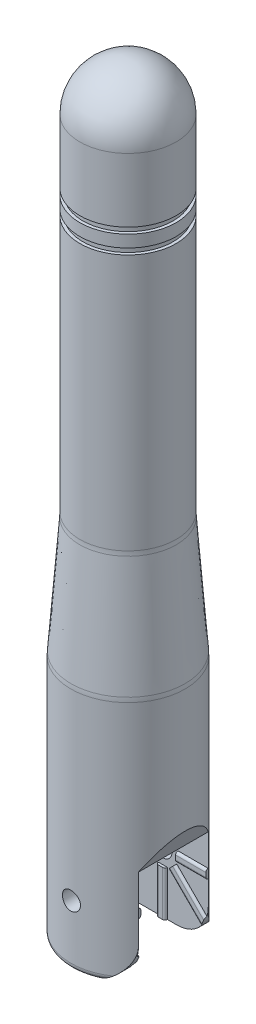
SolidWorks part; units mm, degrees
ref_plane "Plan de face" through (0, 0, 0) normal (0, 0, 1) x (1, 0, 0)
ref_plane "Plan de dessus" through (0, 0, 0) normal (0, 1, 0) x (1, 0, 0)
ref_plane "Plan de droite" through (0, 0, 0) normal (1, 0, 0) x (0, 0, -1)
sketch "Esquisse2" plane through (0, 0, 0) normal (0, 0, 1) x (1, 0, 0)
  line L0 (0, 0) -> (0, 63.1604) construction
  line L1 (0, 63.1604) -> (4, 63.1604) construction
  line L2 (4, 63.1604) -> (4, 0) construction
  line L3 (4, 0) -> (0, 0) construction
  line L4 (4, 0) -> (4.75, 0) construction
  line L5 (4.75, 0) -> (4.75, 20.4) construction
  line L6 (4.75, 20.4) -> (0, 20.4) construction
  line L7 (4, 59.1604) -> (4, 30.5872) construction
  line L8 (4.014, 30.2133) -> (4.736, 20.5867)
  line L9 (4.75, 20.2128) -> (4.75, 0)
  line L10 (4.75, 0) -> (1, 0)
  line L11 (1, 0) -> (1, 59.1604)
  line L12 (1, 59.1604) -> (0, 59.1604)
  line L13 (4, 59.1604) -> (4, 53.8604)
  line L14 (4, 53.8604) -> (3.75, 53.8604)
  line L15 (3.75, 53.8604) -> (3.75, 53.3604)
  line L16 (3.75, 53.3604) -> (4, 53.3604)
  line L17 (4, 53.3604) -> (4, 52.3604)
  line L18 (4, 52.3604) -> (3.75, 52.3604)
  line L19 (3.75, 52.3604) -> (3.75, 51.8604)
  line L20 (3.75, 51.8604) -> (4, 51.8604)
  line L21 (0, 63.1604) -> (0, 59.1604)
  line L22 (4, 51.8604) -> (4, 30.5872)
  arc A0 (0, 63.1604) -> (4, 59.1604) centre (0, 59.1604) cw
  arc A1 (4.75, 20.2128) -> (4.736, 20.5867) centre (-0.25, 20.2128) ccw
  arc A2 (4.014, 30.2133) -> (4, 30.5872) centre (9, 30.5872) cw
  point P18 (4, 30.4)
  point P25 (3.875, 52.3604)
  dimension "D7" = 5
  dimension "D1" = 63.1604
  dimension "D2" = 8
  dimension "D3" = 9.5
  dimension "D4" = 20.4
  dimension "D5" = 2
  dimension "D6" = 10
  dimension "D8" = 9.3
  dimension "D9" = 0.5
  dimension "D10" = 1.5
  dimension "D11" = 7.5
revolve "Révolution1" add sketch "Esquisse2" angle 360 about L0
sketch "Esquisse3" plane through (0, 0, 0) normal (0, -1, 0) x (1, 0, 0)
  line L0 (0, 0) -> (-2.75, 0) construction
  line L1 (-2.75, 2.9) -> (4.75, 2.9)
  line L2 (-2.75, 2.9) -> (-2.75, -2.9)
  line L3 (-2.75, -2.9) -> (4.75, -2.9)
  line L4 (4.75, 2.9) -> (4.75, -2.9)
  line L5 (-4.75, 0) -> (-2.75, 0) construction
  circle A0 centre (0, 0) radius 4.75 construction
  dimension "D1" = 5.8
  dimension "D2" = 2
extrude "Enlèv. mat.-Extru.1" cut sketch "Esquisse3" against normal blind 8
fillet "Congé1" radius 0.5 1 edges at (-4.75, 0, 0)
sketch "Esquisse4" plane through (0, 0, 0) normal (0, 0, 1) x (1, 0, 0)
  line L0 (3.762, 8) -> (3.762, 0.5) construction
  line L1 (-4.75, 0) -> (3.762, 0) construction
  line L2 (1.162, 0) -> (3.762, 0)
  line L3 (3.762, 0) -> (3.762, 2.6)
  line L4 (0, 0) -> (0, 5) construction
  line L5 (3.762, 8) -> (4.75, 10)
  line L6 (4.75, 8) -> (4.75, 20.2128) construction
  line L7 (4.75, 10) -> (4.75, 8)
  line L8 (3.762, 8) -> (4.75, 8) construction
  line L9 (4.75, 8) -> (3.762, 8)
  arc A0 (3.762, 2.6) -> (1.162, 0) centre (1.162, 2.6) cw
  circle A1 centre (0, 5) radius 0.75
  dimension "D1" = 2.6
  dimension "D3" = 1.5
  dimension "D2" = 5
  dimension "D4" = 2
extrude "Enlèv. mat.-Extru.2" cut sketch "Esquisse4" against normal through all both and the other way through all
sketch "Esquisse5" plane through (0, 0, -2.9) normal (0, 0, 1) x (1, 0, 0)
  line L0 (-4.25, 0) -> (1.162, 0) construction
  line L1 (-0.375, 0) -> (0.375, 0)
  line L2 (-0.375, 0) -> (-0.375, 3.75)
  line L3 (-0.375, 3.75) -> (0.375, 3.75)
  line L4 (0.375, 0) -> (0.375, 3.75)
  line L5 (0, 5) -> (0, 3.75) construction
  line L6 (0, 5) -> (3.762, 1.238) construction
  line L7 (3.762, 8) -> (3.762, 2.6) construction
  line L8 (0.6187, 3.851) -> (3.4968, 0.9729) construction
  line L9 (0.6187, 3.851) -> (1.149, 4.3813)
  line L10 (3.4968, 0.9729) -> (4.0271, 1.5032)
  line L11 (1.149, 4.3813) -> (4.0271, 1.5032) construction
  line L12 (0.6187, 3.851) -> (4.0271, 1.5032) construction
  line L13 (3.4968, 0.9729) -> (1.149, 4.3813) construction
  line L14 (1.149, 4.3813) -> (4.0271, 1.5032)
  line L15 (0.6187, 3.851) -> (3.4968, 0.9729)
  line L16 (0, 5) -> (3.762, 5) construction
  line L18 (1.25, 4.625) -> (3.762, 4.625)
  line L19 (1.25, 4.625) -> (1.25, 5.375)
  line L20 (1.25, 5.375) -> (3.762, 5.375)
  line L21 (3.762, 4.625) -> (3.762, 5.375)
  line L22 (1.25, 4.625) -> (3.762, 5.375) construction
  line L23 (1.25, 5.375) -> (3.762, 4.625) construction
  point P13 (2.3229, 2.6771)
  point P18 (2.506, 5)
  dimension "D1" = 0.75
  dimension "D2" = 1.25
  dimension "D3" = 45
  dimension "D4" = 1.25
  dimension "D5" = 1.25
extrude "Boss.-Extru.1" add sketch "Esquisse5" along normal blind 0.2
fillet "Congé2" radius 0.2 6 edges at (2.506, 5.375, -2.7) (2.506, 4.625, -2.7) (2.5881, 2.9422, -2.7) (2.0578, 2.4119, -2.7) (-0.375, 1.875, -2.7) (0.375, 1.875, -2.7)
mirror "Symétrie1" about plane through (0, 0, 0) normal (0, 0, 1) of "Congé2", "Boss.-Extru.1"
sketch "Esquisse6" plane through (0, 0, 2.9) normal (0, 0, 1) x (1, 0, 0)
  line L3 (4.0271, 1.5032) -> (3.6581, 1.8723)
  line L4 (3.3199, 1.1497) -> (3.4968, 0.9729)
  line L5 (3.4968, 0.9729) -> (4.0271, 1.5032)
  line L6 (4.0271, 1.5032) -> (3.6581, 1.8723)
  line L7 (3.3199, 1.1497) -> (3.4968, 0.9729)
  line L8 (3.4968, 0.9729) -> (4.0271, 1.5032)
  arc A1 (3.3199, 1.1497) -> (3.6581, 1.8723) centre (1.162, 2.6) ccw
  arc A2 (3.3199, 1.1497) -> (3.6581, 1.8723) centre (1.162, 2.6) ccw
  dimension "D1" = 0
extrude "Enlèv. mat.-Extru.3" cut sketch "Esquisse6" against normal through all
